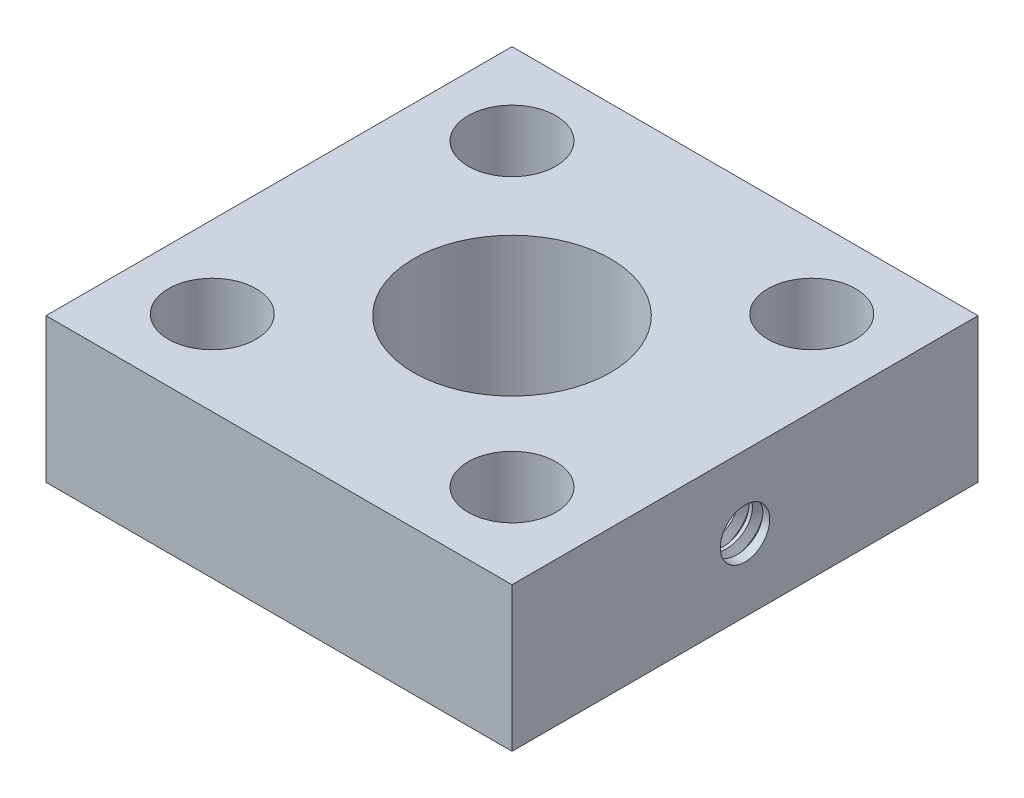
SolidWorks part; units mm, degrees
ref_plane "Front Plane" through (0, 0, 0) normal (0, 0, 1) x (1, 0, 0)
ref_plane "Top Plane" through (0, 0, 0) normal (0, 1, 0) x (1, 0, 0)
ref_plane "Right Plane" through (0, 0, 0) normal (1, 0, 0) x (0, 0, -1)
sketch "Sketch1" plane through (0, 0, 0) normal (0, 1, 0) x (1, 0, 0)
  line L0 (-6.9247, 6.9247) -> (-6.9247, 0) construction
  line L1 (-10.6615, -10.6615) -> (10.6615, -10.6615)
  line L2 (-10.6615, -10.6615) -> (-10.6615, 10.6615)
  line L3 (-10.6615, 10.6615) -> (10.6615, 10.6615)
  line L4 (10.6615, -10.6615) -> (10.6615, 10.6615)
  line L5 (-10.6615, -10.6615) -> (10.6615, 10.6615) construction
  line L6 (-10.6615, 10.6615) -> (10.6615, -10.6615) construction
  line L7 (-6.9247, 0) -> (0, 0) construction
  line L8 (-10.6615, 10.6615) -> (-3.188, 3.188) construction
  circle A0 centre (0, 0) radius 4.5085
  circle A1 centre (-6.9247, 6.9247) radius 2.0066
  circle A2 centre (6.7913, 6.9247) radius 2.0066
  circle A3 centre (6.7913, -6.7913) radius 2.0066
  circle A4 centre (-6.9247, -6.7913) radius 2.0066
  point P0 (0, 0)
  dimension "D1" = 4.0132
  dimension "D2" = 9.017
  dimension "D3" = 2
  dimension "D4" = 2
extrude "Boss-Extrude1" add sketch "Sketch1" along normal blind 3.302 and the other way blind 3.302
sketch "Sketch12" plane through (10.6615, 0, 0) normal (1, 0, 0) x (0, 0, -1)
  circle A0 centre (0, 0) radius 1.1303
  dimension "D1" = 2.2606
extrude "Cut-Extrude2" cut sketch "Sketch12" against normal up to surface (6.297 mm away) up to face at (0, -3.302, 4.5085)
thread "Thread2" pitch 0.635 method cut profile "Thread Profile3" start angle 0, offset 0, length 10, pitch 0.635, diameter 2.2606
ref_plane "Plane3" through (10.6615, 0, 1.1303) normal (0, -1, 0) x (0, 0, 1)
sketch "Thread Profile3" plane through (10.6615, 0, 1.1303) normal (0, -1, 0) x (0, 0, 1)
  line L0 (0, 0) -> (0, 0.635) construction
  line L1 (0, 0) -> (0.3437, 0.1984)
  line L2 (0.3437, 0.1984) -> (0.3437, 0.2778)
  line L3 (0.3437, 0.2778) -> (0, 0.4762)
  line L4 (0.3437, 0.2381) -> (0, 0.2381) construction
  line L11 (0, 0) -> (0, 0.4762)
  point P2 (0, 0)
  dimension "Pitch" = 0.635
  dimension "Profile_Angle" = 60
  dimension "Profile_Land" = 0.0794
  dimension "Profile_Height" = 0.3437
